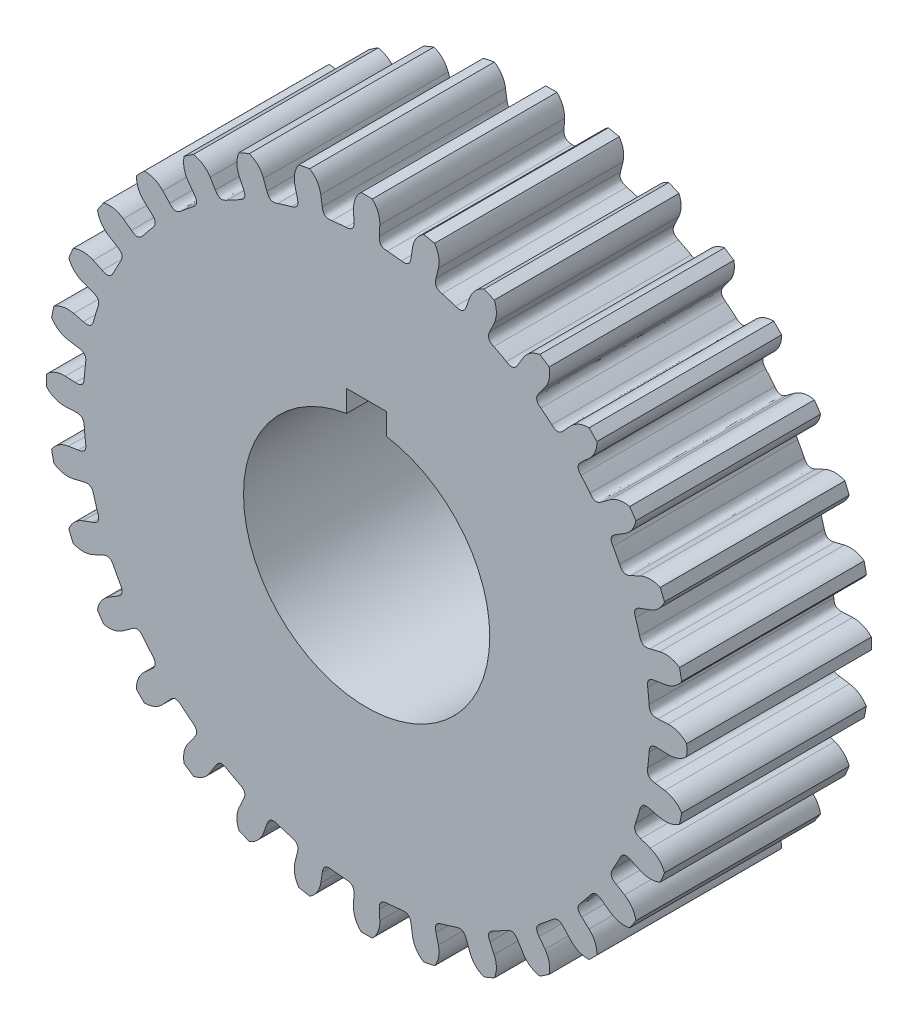
SolidWorks part; units mm, degrees
note: '?' marks a value the reader was unsure of.
ref_plane "Front Plane" through (0, 0, 0) normal (0, 0, 1) x (1, 0, 0)
ref_plane "Top Plane" through (0, 0, 0) normal (0, 1, 0) x (1, 0, 0)
ref_plane "Right Plane" through (0, 0, 0) normal (1, 0, 0) x (0, 0, -1)
sketch "Sketch1" plane through (0, 0, 0) normal (0, 0, 1) x (1, 0, 0)
  line L0 (0, 0) -> (0, 187.5958) construction
  line L1 (0, 0) -> (-4.6515, 266.4862) construction
  line L2 (0, 0) -> (-26.9218, 256.1435) construction
  line L3 (0, 0) -> (-11.106, 254.3693) construction
  line L4 (-1.0687, 24.4767) -> (-1.0032, 22.9781)
  line L5 (-2.4042, 22.874) -> (0, 0)
  line L6 (2.4042, 22.874) -> (0, 0)
  line L7 (1.0687, 24.4767) -> (1.0032, 22.9781)
  circle A0 centre (0, 0) radius 10
  circle A1 centre (0, 0) radius 24.5
  circle A2 centre (0, 0) radius 26
  circle A3 centre (0, 0) radius 23
  arc A4 (-0.4538, 25.996) -> (-1.0687, 24.4767) centre (0.9031, 24.5628) ccw
  arc A5 (0.4538, 25.996) -> (1.0687, 24.4767) centre (-0.9031, 24.5628) cw
  dimension "D1" = 1
  dimension "D4" = 52
  dimension "D5" = 20
  dimension "D6" = 49
  dimension "D7" = 46
  dimension "D2" = 2.5
  dimension "D3" = 6
extrude "Boss-Extrude1" add sketch "Sketch1" along normal mid plane 15 contours L6 A3 L5 A0 | A3 L7 A1 L4 | A5 A2 A4 A1
ref_axis "Axis1" through (0, 0, -8.25) along (0, 0, 1)?
fillet "Fillet1" radius 0.7 2 edges at (-1.0032, 22.9781, 0) (1.0032, 22.9781, 0)
pattern_circular "CirPattern1" count 32 over 360 about axis through (0, 0, -8.25) along (0, 0, 1) of "Boss-Extrude1", "Fillet1"
sketch "Sketch2" plane through (0, 0, -7.5) normal (0, 0, -1) x (-1, 0, 0)
  line L1 (-1.625, 11.625) -> (1.625, 11.625)
  line L2 (-1.625, 11.625) -> (-1.625, 8.375)
  line L3 (-1.625, 8.375) -> (1.625, 8.375)
  line L4 (1.625, 11.625) -> (1.625, 8.375)
  line L5 (-1.625, 11.625) -> (1.625, 8.375) construction
  line L6 (-1.625, 8.375) -> (1.625, 11.625) construction
  circle A0 centre (0, 0) radius 10 construction
  point P0 (0, 10)
  dimension "D1" = 3.25
extrude "Cut-Extrude1" cut sketch "Sketch2" against normal through all
